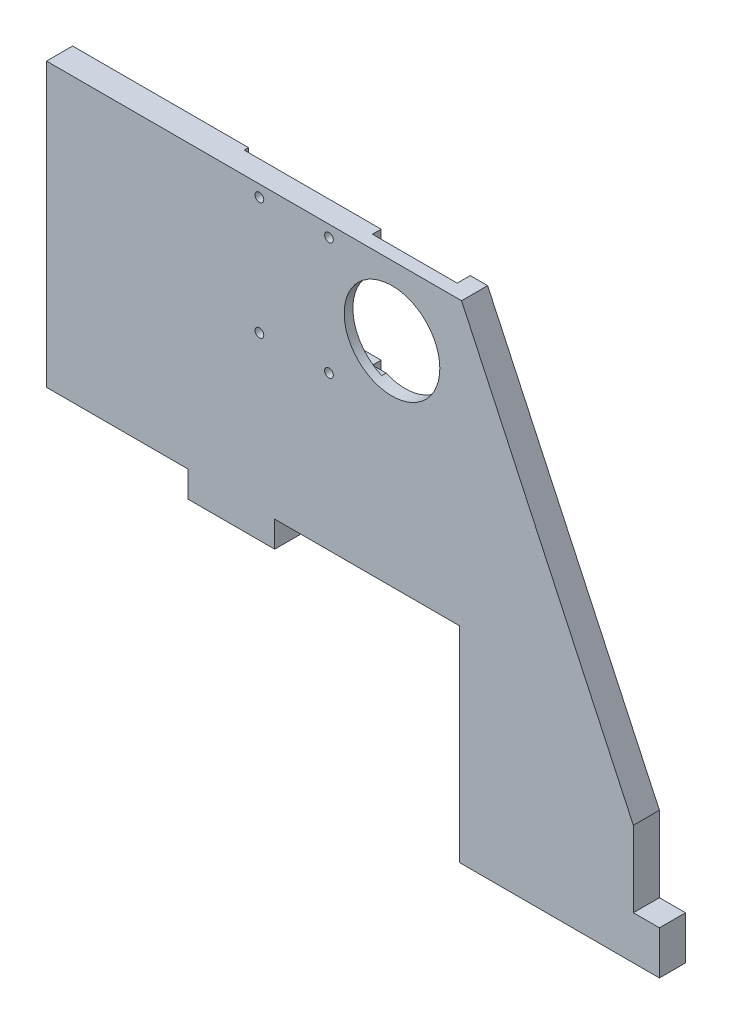
SolidWorks part; units mm, degrees
ref_plane "Plan de face" through (0, 0, 0) normal (0, 0, 1) x (1, 0, 0)
ref_plane "Plan de dessus" through (0, 0, 0) normal (0, 1, 0) x (1, 0, 0)
ref_plane "Plan de droite" through (0, 0, 0) normal (1, 0, 0) x (0, 0, -1)
sketch "Esquisse1" plane through (0, 0, 0) normal (0, 0, 1) x (1, 0, 0)
  line L1 (-67.5, 56.085) -> (67.5, 56.085)
  line L2 (-67.5, 56.085) -> (-67.5, -56.085)
  line L3 (-67.5, -56.085) -> (67.5, -56.085)
  line L4 (67.5, 56.085) -> (67.5, -56.085)
  dimension "D1" = 135
  dimension "D2" = 112.17
  dimension "D3" = 67.5
  dimension "D4" = 56.085
extrude "Boss.-Extru.1" add sketch "Esquisse1" along normal blind 6
sketch "Esquisse2" plane through (0, 0, 6) normal (0, 0, 1) x (1, 0, 0)
  line L0 (-67.5, -56.085) -> (67.5, -56.085) construction
  line L1 (27.5, -56.085) -> (-67.5, -56.085)
  line L2 (27.5, -56.085) -> (27.5, -8.915)
  line L3 (-38.5, -8.915) -> (27.5, -8.915)
  line L4 (-67.5, -56.085) -> (-67.5, -8.915)
  line L5 (-67.5, 56.085) -> (-67.5, -56.085) construction
  line L7 (67.5, -28.665) -> (27.9804, 56.085)
  line L8 (-38.5, -8.915) -> (-67.5, -8.915)
  line L9 (67.5, -56.085) -> (67.5, 56.085) construction
  line L10 (67.5, 56.085) -> (-67.5, 56.085) construction
  line L11 (27.9804, 56.085) -> (67.5, 56.085)
  line L12 (67.5, 56.085) -> (67.5, -28.665)
  dimension "D1" = 47.17
  dimension "D2" = 95
  dimension "D3" = 27.42
  dimension "D4" = 155
  dimension "D5" = 115
extrude "Enlèv. mat.-Extru.1" cut sketch "Esquisse2" against normal blind 6
sketch "Esquisse3" plane through (0, 0, 6) normal (0, 0, 1) x (1, 0, 0)
  line L0 (67.5, -56.085) -> (67.5, -28.665) construction
  line L1 (67.5, -56.085) -> (73.5, -56.085)
  line L2 (67.5, -56.085) -> (67.5, -46.085)
  line L3 (67.5, -46.085) -> (73.5, -46.085)
  line L4 (73.5, -56.085) -> (73.5, -46.085)
  line L6 (-35, -8.915) -> (-15, -8.915)
  line L7 (-35, -8.915) -> (-35, -14.915)
  line L8 (-35, -14.915) -> (-15, -14.915)
  line L9 (-15, -8.915) -> (-15, -14.915)
  line L10 (27.5, -8.915) -> (-67.5, -8.915) construction
  line L16 (27.5, -56.085) -> (27.5, -8.915) construction
  dimension "D3" = 6
  dimension "D4" = 20
  dimension "D5" = 42.5
  dimension "D6" = 10
  dimension "D7" = 6
extrude "Boss.-Extru.2" add sketch "Esquisse3" against normal blind 6
sketch "Esquisse4" plane through (0, 0, 0) normal (0, 0, -1) x (-1, 0, 0)
  line L0 (-27.9804, 56.085) -> (67.5, 56.085) construction
  line L1 (-23.9804, 56.085) -> (27.0196, 56.085)
  line L2 (-23.9804, 56.085) -> (-23.9804, 24.085)
  line L3 (-23.9804, 24.085) -> (27.0196, 24.085)
  line L4 (27.0196, 56.085) -> (27.0196, 24.085)
  dimension "D1" = 4
  dimension "D2" = 51
  dimension "D3" = 32
extrude "Enlèv. mat.-Extru.5" cut sketch "Esquisse4" against normal blind 3
sketch "Esquisse7" plane through (0, 0, 3) normal (0, 0, -1) x (-1, 0, 0)
  line L0 (-23.9804, 56.085) -> (-23.9804, 24.085) construction
  line L1 (27.0196, 56.085) -> (-23.9804, 56.085) construction
  circle A0 centre (-11.9804, 40.085) radius 11
  dimension "D1" = 22
  dimension "D2" = 12
  dimension "D3" = 16
extrude "Enlèv. mat.-Extru.6" cut sketch "Esquisse7" against normal through all
sketch "Esquisse8" plane through (0, 0, 3) normal (0, 0, -1) x (-1, 0, 0)
  line L1 (-9.4804, 50.185) -> (20.5196, 50.185)
  line L2 (-9.4804, 50.185) -> (-9.4804, 29.985)
  line L3 (-9.4804, 29.985) -> (20.5196, 29.985)
  line L4 (20.5196, 50.185) -> (20.5196, 29.985)
  circle A0 centre (-11.9804, 40.085) radius 11 construction
  dimension "D1" = 30
  dimension "D2" = 20.2
  dimension "D3" = 10.1
  dimension "D4" = 32.5
extrude "Enlèv. mat.-Extru.7" cut sketch "Esquisse8" against normal blind 1
sketch "Esquisse9" plane through (0, 0, 3) normal (0, 0, -1) x (-1, 0, 0)
  line L0 (27.0196, 56.085) -> (-23.9804, 56.085) construction
  line L1 (-4.4804, 56.085) -> (20.5196, 56.085)
  line L2 (-4.4804, 56.085) -> (-4.4804, 50.185)
  line L3 (-4.4804, 50.185) -> (20.5196, 50.185)
  line L4 (20.5196, 56.085) -> (20.5196, 50.185)
  dimension "D1" = 25
extrude "Boss.-Extru.4" add sketch "Esquisse9" along normal blind 2
sketch "Esquisse10" plane through (0, 0, 3) normal (0, 0, -1) x (-1, 0, 0)
  line L0 (-23.9804, 24.085) -> (27.0196, 24.085) construction
  line L1 (20.5196, 29.985) -> (-4.4804, 29.985)
  line L2 (20.5196, 29.985) -> (20.5196, 24.085)
  line L3 (20.5196, 24.085) -> (-4.4804, 24.085)
  line L4 (-4.4804, 29.985) -> (-4.4804, 24.085)
  dimension "D1" = 25
extrude "Boss.-Extru.5" add sketch "Esquisse10" along normal blind 2
sketch "Esquisse11" plane through (0, 0, 3) normal (0, 0, -1) x (-1, 0, 0)
  line L1 (20.5196, 56.085) -> (27.0196, 56.085)
  line L2 (20.5196, 56.085) -> (20.5196, 24.085)
  line L3 (20.5196, 24.085) -> (27.0196, 24.085)
  line L4 (27.0196, 56.085) -> (27.0196, 24.085)
extrude "Boss.-Extru.6" add sketch "Esquisse11" along normal blind 2
sketch "Esquisse12" plane through (0, 0, 1) normal (0, 0, -1) x (-1, 0, 0)
  line L0 (27.0196, 24.085) -> (27.0196, 56.085) construction
  line L1 (27.0196, 24.085) -> (27.0196, 56.085) construction
  line L2 (27.0196, 56.085) -> (-4.4804, 56.085) construction
  line L3 (20.5196, 29.985) -> (-4.4804, 29.985) construction
  circle A0 centre (2.5196, 53.435) radius 1
  circle A1 centre (18.5196, 53.435) radius 1
  circle A2 centre (2.5196, 26.435) radius 1
  circle A3 centre (18.5196, 26.435) radius 1
  dimension "D1" = 2
  dimension "D2" = 2
  dimension "D3" = 2
  dimension "D4" = 2
  dimension "D5" = 16
  dimension "D6" = 16
  dimension "D7" = 8.5
  dimension "D8" = 8.5
  dimension "D9" = 2.65
  dimension "D10" = 2.65
  dimension "D11" = 3.55
  dimension "D12" = 3.55
extrude "Enlèv. mat.-Extru.8" cut sketch "Esquisse12" against normal through all
equation "\"D3@Esquisse1\"=\"D1@Esquisse1\"/2"
equation "\"D4@Esquisse1\"=\"D2@Esquisse1\"/2"
